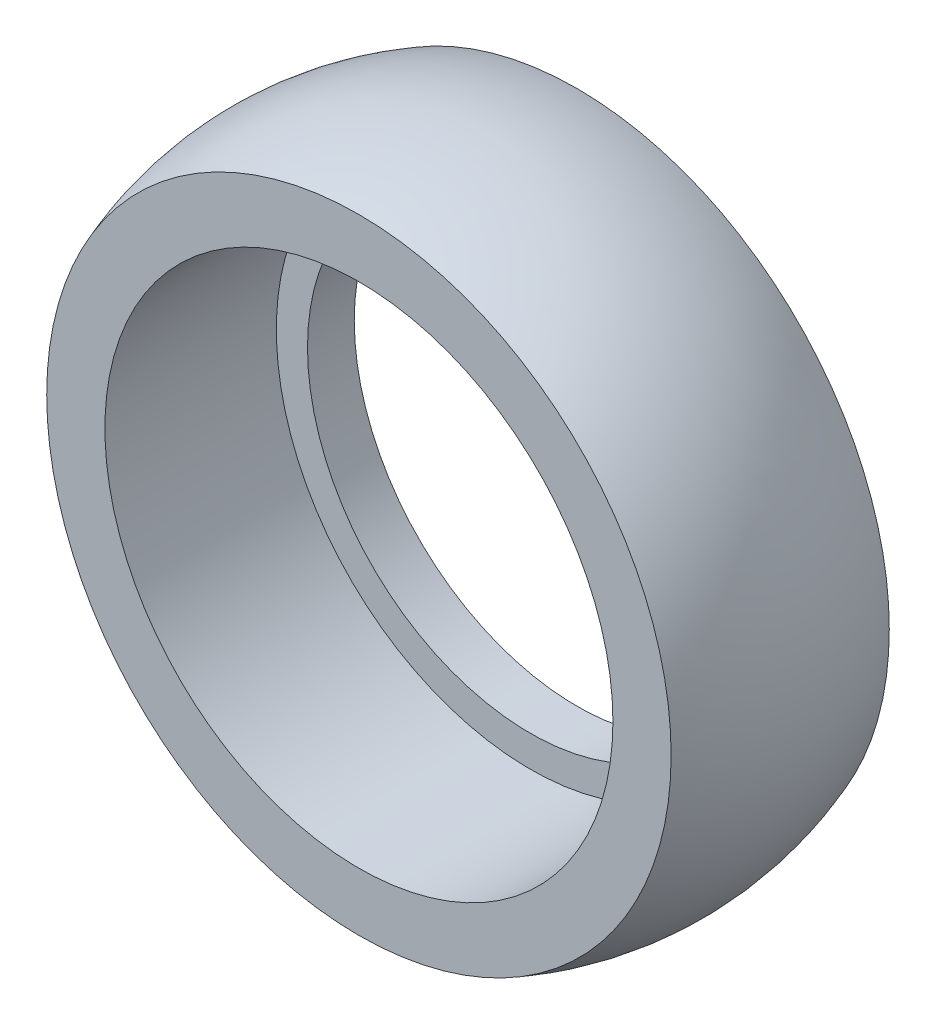
SolidWorks part; units mm, degrees
material "ABS"
ref_plane "Front (1)" through (0, 0, 0) normal (0, 0, 1) x (1, 0, 0)
ref_plane "Top (2)" through (0, 0, 0) normal (0, 1, 0) x (1, 0, 0)
ref_plane "Right (3)" through (0, 0, 0) normal (1, 0, 0) x (0, 0, -1)
ref_axis "X Axis" through (13.5064, 0, 0) along (-1, 0, 0)
ref_axis "Y Axis" through (0, 12.3593, 0) along (0, -1, 0)
ref_axis "Z Axis" through (0, 0, 14.1119) along (0, 0, -1)
sketch "Sketch2" plane through (0, 0, 0) normal (1, 0, 0) x (0, 0, -1)
  line L0 (0, 0) -> (8.188, 0) construction
  line L1 (-3.5, 10.0175) -> (-3.5, 8.15) construction
  line L2 (-7, 10.0175) -> (0, 10.0175) construction
  line L3 (-7, 10.0175) -> (-7, 8.15)
  line L4 (-1.5, 7.15) -> (0, 7.15)
  line L5 (0, 10.0175) -> (0, 7.15)
  line L8 (-7, 8.15) -> (-1.5, 8.15)
  line L9 (-1.5, 7.15) -> (-1.5, 8.15)
  arc A0 (0, 10.0175) -> (-7, 10.0175) centre (-3.5, 0.65) ccw
  dimension "D6" = 10
  dimension "D1" = 16.3
  dimension "D2" = 4
  dimension "D3" = 7
  dimension "D4" = 21.3
  dimension "D5" = 1
  dimension "D7" = 2.5
revolve "Revolve1" add sketch "Sketch2" angle 360 about L0
